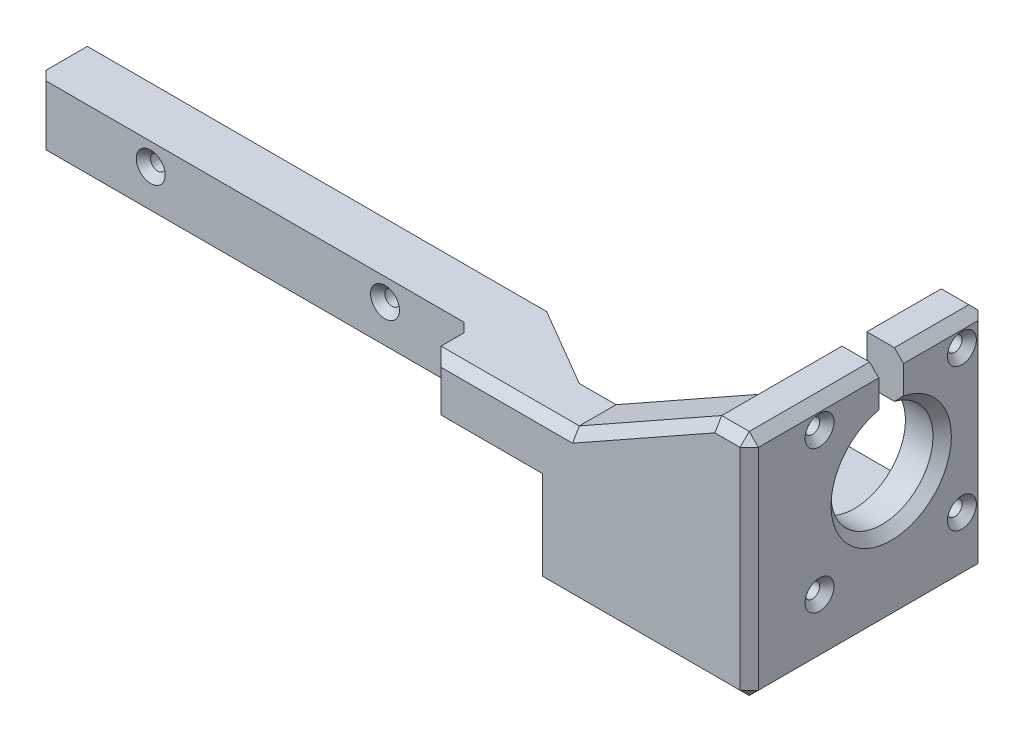
SolidWorks part; units mm, degrees
ref_plane "Front Plane" through (0, 0, 0) normal (0, 0, 1) x (1, 0, 0)
ref_plane "Top Plane" through (0, 0, 0) normal (0, 1, 0) x (1, 0, 0)
ref_plane "Right Plane" through (0, 0, 0) normal (1, 0, 0) x (0, 0, -1)
sketch "Sketch1" plane through (0, 0, 0) normal (0, 0, 1) x (1, 0, 0)
  line L0 (-50, 0) -> (50, 0) construction
  line L1 (-50, -6.5) -> (50, -6.5)
  line L2 (-50, -6.5) -> (-50, 6.5)
  line L3 (-50, 6.5) -> (50, 6.5)
  line L4 (50, -6.5) -> (50, 6.5)
  line L5 (0, -6.5) -> (0, 6.5) construction
  circle A8 centre (25.8, 1.7) radius 1.6
  circle A9 centre (-25.2, 1.7) radius 1.6
  point P0 (0, 0)
  point P6 (-50, 0)
  point P7 (0, -6.5)
  point P16 (0, 0)
  dimension "D4" = 24.2
  dimension "D6" = 51
  dimension "D3" = 3.2
  dimension "D1" = 13
  dimension "D2" = 100
  dimension "D5" = 8.2
extrude "Boss-Extrude1" add sketch "Sketch1" along normal blind 10
sketch "Sketch2" plane through (0, 0, 10) normal (0, 0, 1) x (1, 0, 0)
  line L0 (50, -6.5) -> (106.1, -6.5)
  line L1 (106.1, -6.5) -> (106.1, 6.5)
  line L2 (106.1, 6.5) -> (50, 6.5)
  line L4 (50, -6.5) -> (50, 6.5)
  line L5 (50, 6.5) -> (-50, 6.5)
  line L6 (-50, 6.5) -> (-50, -6.5)
  line L7 (-50, -6.5) -> (50, -6.5)
  line L8 (50, -6.5) -> (50, 6.5) construction
  line L9 (50, 6.5) -> (-50, 6.5)
  line L10 (-50, 6.5) -> (-50, -6.5)
  line L11 (-50, -6.5) -> (50, -6.5)
  circle A0 centre (25.8, 1.7) radius 1.6 construction
  circle A1 centre (-25.2, 1.7) radius 1.6 construction
  circle A8 centre (25.8, 1.7) radius 1.6
  circle A9 centre (-25.2, 1.7) radius 1.6
  dimension "D2" = 56.1
  dimension "D1" = 0
extrude "Boss-Extrude2" add sketch "Sketch2" along normal blind 10
sketch "Sketch4" plane through (106.1, 0, 0) normal (1, 0, 0) x (0, 0, -1)
  line L0 (-20, -6.5) -> (-20, -17.85)
  line L1 (-20, -17.85) -> (31.8, -17.85)
  line L2 (31.8, -17.85) -> (31.8, 23.95)
  line L3 (31.8, 23.95) -> (-20, 23.95)
  line L4 (-20, 23.95) -> (-20, -6.5)
  line L6 (-10, 23.95) -> (-10, -17.85) construction
  line L7 (31.8, 3.05) -> (-10, 3.05) construction
  line L8 (10.8, -17.85) -> (10.8, 23.95) construction
  circle A0 centre (-4.7, 18.55) radius 1.6
  circle A1 centre (26.3, 18.55) radius 1.6
  circle A2 centre (26.3, -12.45) radius 1.6
  circle A3 centre (-4.7, -12.45) radius 1.6
  circle A4 centre (10.9, 3.05) radius 11.1
  dimension "D8" = 3.2
  dimension "D9" = 22.2
  dimension "D1" = 11.35
  dimension "D2" = 51.8
  dimension "D3" = 41.8
  dimension "D4" = 41.8
  dimension "D5" = 21
  dimension "D6" = 15.5
  dimension "D7" = 15.5
extrude "Boss-Extrude3" add sketch "Sketch4" along normal blind 8
sketch "Sketch5" plane through (0, -17.85, 0) normal (0, -1, 0) x (1, 0, 0)
  line L0 (-50, 20) -> (106.1, 20) construction
  line L1 (114.1, -31.8) -> (67.1, -31.8)
  line L2 (114.1, -31.8) -> (114.1, 20)
  line L3 (114.1, 20) -> (67.1, 20)
  line L4 (67.1, -31.8) -> (67.1, 20)
  dimension "D1" = 47
extrude "Boss-Extrude4" add sketch "Sketch5" along normal blind 8
sketch "Sketch6" plane through (0, 0, 20) normal (0, 0, 1) x (1, 0, 0)
  line L0 (106.1, 23.95) -> (75.1, 6.5)
  line L1 (67.1, -17.85) -> (106.1, -17.85)
  line L2 (67.1, -17.85) -> (67.1, -6.5)
  line L3 (67.1, -6.5) -> (106.1, -6.5)
  line L4 (106.1, -17.85) -> (106.1, -6.5)
  line L5 (106.1, 6.5) -> (-50, 6.5) construction
  line L6 (75.1, 6.5) -> (106.1, 6.5)
  line L7 (106.1, 6.5) -> (106.1, 23.95)
extrude "Boss-Extrude5" add sketch "Sketch6" against normal up to surface (10 mm away) up to face at (78.05, 0, 10)
sketch "Sketch7" plane through (0, 0, -31.8) normal (0, 0, -1) x (-1, 0, 0)
  line L0 (-75.1, 6.5) -> (-106.1, 23.95) construction
  line L1 (-114.1, 23.95) -> (-106.1, 23.95) construction
  line L2 (-67.1, -6.5) -> (-67.1, 1.9968)
  line L3 (-67.1, -25.85) -> (-67.1, -17.85) construction
  line L4 (-67.1, -25.85) -> (-114.1, -25.85) construction
  line L5 (-114.1, -25.85) -> (-114.1, 23.95) construction
  line L6 (-67.1, 1.9968) -> (-106.1, 23.95)
  line L7 (-114.1, 23.95) -> (-106.1, 23.95)
  line L9 (-67.1, -25.85) -> (-67.1, -17.85)
  line L10 (-67.1, -25.85) -> (-114.1, -25.85)
  line L11 (-114.1, -25.85) -> (-114.1, 23.95)
  line L12 (-67.1, -6.5) -> (-67.1, -17.85)
extrude "Boss-Extrude6" add sketch "Sketch7" along normal blind 8
sketch "Sketch8" plane through (0, -25.85, 0) normal (0, -1, 0) x (1, 0, 0)
  line L0 (114.1, -39.8) -> (114.1, 20) construction
  line L2 (67.1, 20) -> (114.1, 20) construction
  line L3 (67.1, 20) -> (67.1, -31.8) construction
  line L4 (67.1, -31.8) -> (114.1, -31.8) construction
  line L6 (114.1, 20) -> (114.1, -31.8) construction
  line L7 (73.85, 12.05) -> (83.85, 12.05)
  line L8 (73.85, 12.05) -> (73.85, 2.05)
  line L9 (73.85, 2.05) -> (83.85, 2.05)
  line L10 (83.85, 12.05) -> (83.85, 2.05)
  line L11 (73.85, 12.05) -> (83.85, 2.05) construction
  line L12 (73.85, 2.05) -> (83.85, 12.05) construction
  line L13 (114.1, -39.8) -> (67.1, -39.8) construction
  line L26 (90.6, 20) -> (90.6, -5.9) construction
  line L27 (67.1, -5.9) -> (90.6, -5.9) construction
  line L28 (107.35, 2.05) -> (97.35, 2.05)
  line L29 (97.35, 12.05) -> (97.35, 2.05)
  line L30 (107.35, 12.05) -> (97.35, 12.05)
  line L31 (107.35, 12.05) -> (107.35, 2.05)
  line L32 (107.35, -23.85) -> (107.35, -13.85)
  line L33 (107.35, -23.85) -> (97.35, -23.85)
  line L34 (97.35, -23.85) -> (97.35, -13.85)
  line L35 (107.35, -13.85) -> (97.35, -13.85)
  line L36 (73.85, -13.85) -> (83.85, -13.85)
  line L37 (83.85, -23.85) -> (83.85, -13.85)
  line L38 (73.85, -23.85) -> (83.85, -23.85)
  line L39 (73.85, -23.85) -> (73.85, -13.85)
  point P1 (78.85, 7.05)
  point P14 (0, 0)
  point P16 (102.35, 5.05)
  point P18 (78.85, -5.9)
  point P19 (0, 0)
  point P20 (90.6, 7.05)
  dimension "D1" = 10
  dimension "D2" = 10
  dimension "D3" = 8
extrude "Boss-Extrude7" add sketch "Sketch8" along normal blind 2.15
chamfer "Chamfer1" distance 10 angle 59.68 1 edges at (50, 0, 10) first distance on face at (50, 0, 5)
chamfer "Chamfer3" distance 2 angle 45 12 edges at (114.1, -25.85, -9.9) (114.1, -0.95, 20) (114.1, -0.95, -39.8) (114.1, 23.95, -9.9) (-50, 0, 20) (67.1, -16.175, 20) (90.6, -25.85, -39.8) (90.6, -25.85, 20) (86.6, 12.9734, -39.8) (110.1, 23.95, -39.8) (110.1, 23.95, 20) (114.1, 3.05, -22)
chamfer "Chamfer4" distance 3 angle 45 16 edges at (102.35, -28, 2.05) (97.35, -28, 7.05) (102.35, -28, 12.05) (107.35, -28, 7.05) (78.85, -28, 2.05) (73.85, -28, 7.05) (78.85, -28, 12.05) (83.85, -28, 7.05) (97.35, -28, -18.85) (102.35, -28, -13.85) (107.35, -28, -18.85) (102.35, -28, -23.85) (78.85, -28, -13.85) (83.85, -28, -18.85) (78.85, -28, -23.85) (73.85, -28, -18.85)
chamfer "Chamfer5" distance 1.55 angle 45 4 edges at (114.1, -12.45, 6.3) (114.1, -12.45, -27.9) (114.1, 18.55, -24.7) (114.1, 18.55, 3.1)
sketch "Sketch9" plane through (0, 6.5, 0) normal (0, 1, 0) x (1, 0, 0)
  line L1 (45, -20) -> (-50, -20)
  line L2 (45, -20) -> (45, -11)
  line L3 (45, -11) -> (-50, -11)
  line L4 (-50, -20) -> (-50, -11)
  line L5 (-50, -18) -> (-50, 0) construction
  dimension "D1" = 95
  dimension "D2" = 9
extrude "Cut-Extrude1" cut sketch "Sketch9" against normal through all
chamfer "Chamfer6" distance 1.55 angle 45 2 edges at (24.2, 1.7, 11) (-26.8, 1.7, 11)
chamfer "Chamfer7" distance 2 angle 45 6 edges at (45, 0, 20) (45, 0, 11) (-50, 0, 11) (88.8235, 14.225, 20) (57.05, -6.5, 20) (60.05, 6.5, 20)
sketch "Sketch11" plane through (0, 23.95, 0) normal (0, 1, 0) x (1, 0, 0)
  line L0 (67.1, 39.8) -> (106.6242, 39.8) construction
  line L1 (67.1, 31.8) -> (114.1, 31.8)
  line L2 (67.1, 31.8) -> (67.1, 39.8)
  line L3 (67.1, 39.8) -> (114.1, 39.8)
  line L4 (114.1, 31.8) -> (114.1, 39.8)
  line L5 (114.1, 37.8) -> (114.1, -18) construction
  point P9 (0, 0)
extrude "Cut-Extrude3" cut sketch "Sketch11" against normal through all
sketch "Sketch13" plane through (114.1, 0, 0) normal (1, 0, 0) x (0, 0, -1)
  line L6 (13.6, 13.8166) -> (13.6, 23.95)
  line L7 (8.2, 13.8166) -> (8.2, 23.95)
  line L8 (13.6, 23.95) -> (8.2, 23.95)
  circle A2 centre (10.9, 3.05) radius 11.1 construction
  arc A3 (13.6, 13.8166) -> (8.2, 13.8166) centre (10.9, 3.05) ccw
extrude "Cut-Extrude4" cut sketch "Sketch13" against normal through all
chamfer "Chamfer9" distance 2 angle 45 3 edges at (67.1, -21.85, -31.8) (109.1, 23.95, -31.8) (114.1, -0.95, -31.8)
